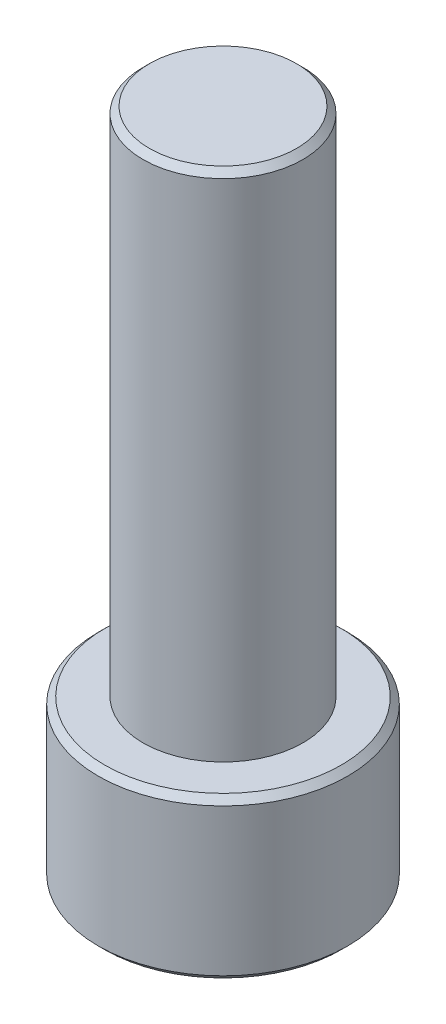
SolidWorks part; units mm, degrees
ref_plane "Спереди" through (0, 0, 0) normal (0, 0, 1) x (1, 0, 0)
ref_plane "Сверху" through (0, 0, 0) normal (0, 1, 0) x (1, 0, 0)
ref_plane "Справа" through (0, 0, 0) normal (1, 0, 0) x (0, 0, -1)
sketch "Эскиз1" plane through (0, 0, 0) normal (0, 1, 0) x (1, 0, 0)
  line L1 (0, 1.1547) -> (-1, 0.5774)
  line L2 (-1, 0.5774) -> (-1, -0.5774)
  line L3 (-1, -0.5774) -> (0, -1.1547)
  line L4 (0, -1.1547) -> (1, -0.5774)
  line L5 (1, -0.5774) -> (1, 0.5774)
  line L6 (1, 0.5774) -> (0, 1.1547)
  circle A0 centre (0, 0) radius 1.95
  circle A1 centre (0, 0) radius 1 construction
  circle A2 centre (0, 0) radius 1.25
extrude "Бобышка-Вытянуть1" add sketch "Эскиз1" against normal blind 2.5 contours A0 A2 | A2 L6 L5 L4 L3 L2 L1 | L5 L6 L1 L2 L3 L4 region at (0, 0, 0) region at (-1.8948, 0, 0) region at (-1.2146, 0, 0)
extrude "Бобышка-Вытянуть2" add sketch "Эскиз1<3>" along normal blind 8 contours A2 L6 L5 L4 L3 L2 L1 | L5 L6 L1 L2 L3 L4 region at (0, 0, 0) region at (-1.2146, 0, 0)
sketch "Эскиз1<3>" plane through (0, 0, 0) normal (0, 1, 0) x (1, 0, 0) same geometry as "Эскиз1"
extrude "Вырез-Вытянуть1" cut sketch "Эскиз1<6>" against normal through all from offset 1.25 contours L5 L6 L1 L2 L3 L4 offset against normal yes
sketch "Эскиз1<6>" plane through (0, 0, 0) normal (0, 1, 0) x (1, 0, 0) same geometry as "Эскиз1"
chamfer "Фаска1" distance 0.1 angle 45 3 edges at (0, 8, 1.25) (0, 0, 1.95) (0, -2.5, 1.95)
